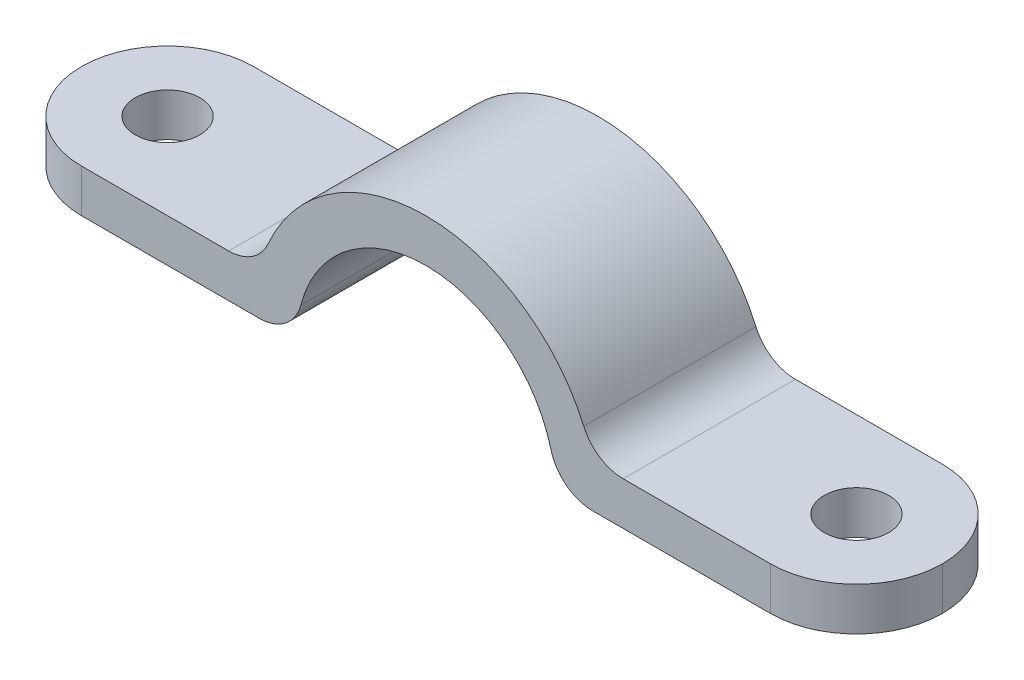
SolidWorks part; units mm, degrees
ref_plane "Front Plane" through (0, 0, 0) normal (0, 0, 1) x (1, 0, 0)
ref_plane "Top Plane" through (0, 0, 0) normal (0, 1, 0) x (1, 0, 0)
ref_plane "Right Plane" through (0, 0, 0) normal (1, 0, 0) x (0, 0, -1)
sketch "Sketch1" plane through (0, 0, 0) normal (0, 0, 1) x (1, 0, 0)
  line L0 (-100, 0) -> (-38.7298, 0)
  line L1 (38.7298, 0) -> (100, 0)
  line L2 (-100, 10) -> (-45.8258, 10)
  line L3 (45.8258, 10) -> (100, 10)
  line L4 (-100, 10) -> (-100, 0)
  line L5 (100, 10) -> (100, 0)
  line L6 (30, 0) -> (100, 0) construction
  line L7 (38.7298, 10) -> (100, 10) construction
  line L8 (-100, 0) -> (-30, 0) construction
  line L9 (-100, 10) -> (-38.7298, 10) construction
  arc A0 (29.0474, 7.5) -> (-29.0474, 7.5) centre (0, 0) ccw
  arc A1 (36.6606, 16) -> (-36.6606, 16) centre (0, 0) ccw
  arc A2 (30, 0) -> (-30, 0) centre (0, 0) ccw construction
  arc A3 (29.0474, 7.5) -> (38.7298, 0) centre (38.7298, 10) ccw
  arc A4 (38.7298, 10) -> (-38.7298, 10) centre (0, 0) ccw construction
  arc A5 (36.6606, 16) -> (45.8258, 10) centre (45.8258, 20) ccw
  arc A6 (-29.0474, 7.5) -> (-38.7298, 0) centre (-38.7298, 10) cw
  arc A7 (-45.8258, 10) -> (-36.6606, 16) centre (-45.8258, 20) ccw
  point P14 (30, 0)
  dimension "D2" = 60
  dimension "D4" = 10
  dimension "D1" = 200
  dimension "D3" = 10
extrude "Boss-Extrude1" add sketch "Sketch1" along normal blind 40
fillet "Fillet1" radius 20 4 edges at (100, 5, 0) (100, 5, 40) (-100, 5, 0) (-100, 5, 40)
sketch "Sketch2" plane through (0, 10, 0) normal (0, 1, 0) x (1, 0, 0)
  circle A0 centre (-80, -20) radius 7.5
  circle A1 centre (80, -20) radius 7.5
  dimension "D1" = 15
  dimension "D2" = 15
extrude "Cut-Extrude1" cut sketch "Sketch2" against normal blind 40
